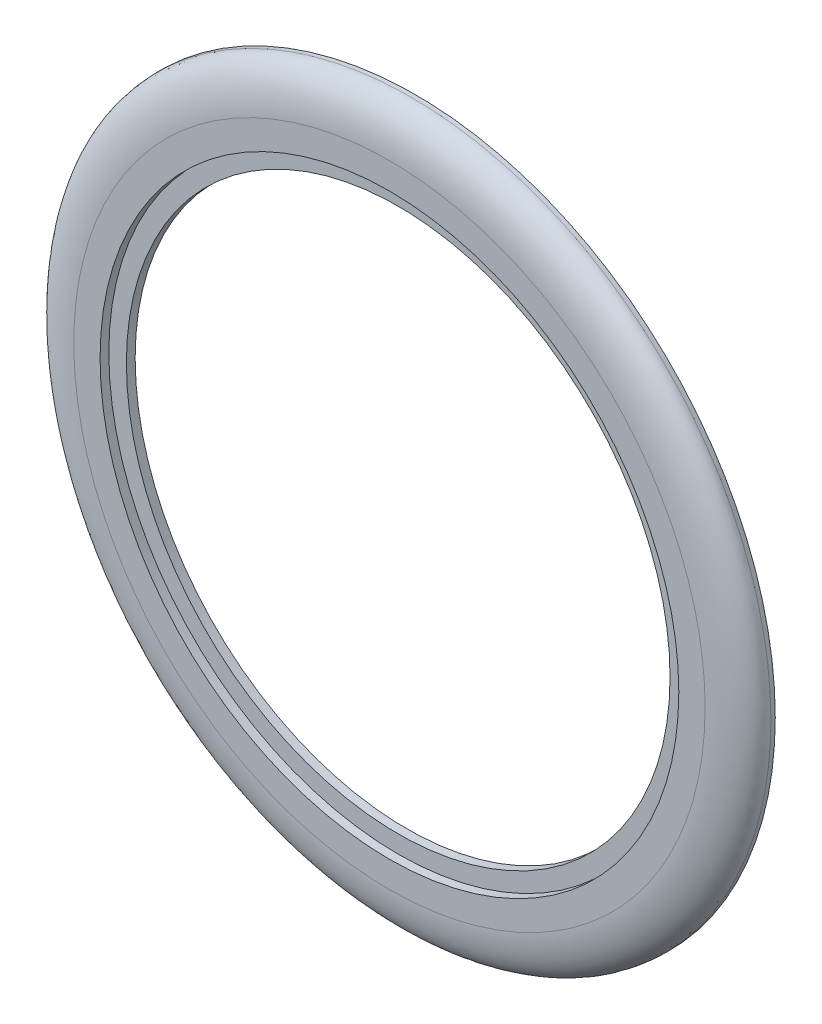
SolidWorks part; units mm, degrees
ref_plane "Ebene vorne" through (0, 0, 0) normal (0, 0, 1) x (1, 0, 0)
ref_plane "Ebene oben" through (0, 0, 0) normal (0, 1, 0) x (1, 0, 0)
ref_plane "Ebene rechts" through (0, 0, 0) normal (1, 0, 0) x (0, 0, -1)
sketch "Sketch1" plane through (0, 0, 0) normal (0, 0, 1) x (1, 0, 0)
  circle A0 centre (0, 0) radius 20.5
  dimension "D1" = 41
extrude "Boss-Extrude1" add sketch "Sketch1" along normal blind 1.5
fillet "Fillet1" radius 1.25 1 edges at (20.5, 0, 1.5) second distance 2.5 first distance on face at (20.5, 0, 1.5)
sketch "Sketch2" plane through (0, 0, 1.5) normal (0, 0, 1) x (1, 0, 0)
  circle A0 centre (0, 0) radius 16.5
  dimension "D1" = 33
extrude "Cut-Extrude1" cut sketch "Sketch2" against normal blind 0.5
sketch "Sketch3" plane through (0, 0, 1) normal (0, 0, 1) x (1, 0, 0)
  circle A0 centre (0, 0) radius 15.5
  dimension "D1" = 31
extrude "Cut-Extrude2" cut sketch "Sketch3" against normal through all
sketch "Sketch4" plane through (0, 0, 0) normal (0, 0, -1) x (-1, 0, 0)
  circle A0 centre (0, 0) radius 18
  dimension "D1" = 36
extrude "Cut-Extrude3" cut sketch "Sketch4" against normal blind 0.5
